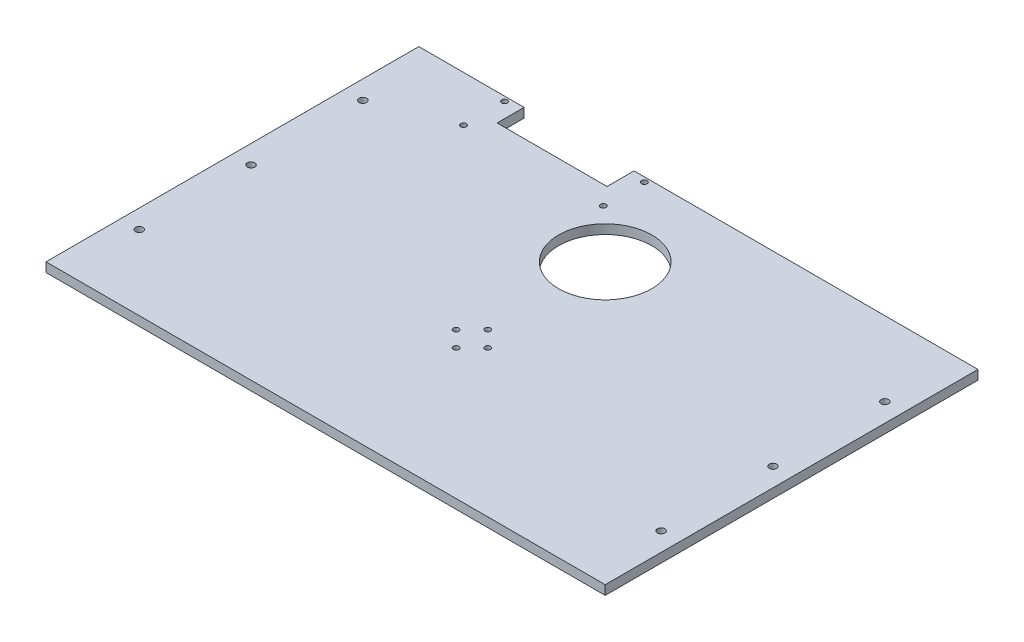
SolidWorks part; units mm, degrees
ref_plane "前视基准面" through (0, 0, 0) normal (0, 0, 1) x (1, 0, 0)
ref_plane "上视基准面" through (0, 0, 0) normal (0, 1, 0) x (1, 0, 0)
ref_plane "右视基准面" through (0, 0, 0) normal (1, 0, 0) x (0, 0, -1)
sketch "Sketch1" plane through (0, 0, 0) normal (0, 1, 0) x (1, 0, 0)
  line L1 (-150, 100) -> (150, 100)
  line L2 (-150, 100) -> (-150, -100)
  line L3 (-150, -100) -> (150, -100)
  line L4 (150, 100) -> (150, -100)
  line L5 (-150, 100) -> (150, -100) construction
  line L6 (-150, -100) -> (150, 100) construction
  point P0 (0, 0)
  dimension "D1" = 200
  dimension "D2" = 300
extrude "Boss-Extrude1" add sketch "Sketch1" along normal blind 5
sketch "Sketch2" plane through (0, 5, 0) normal (0, 1, 0) x (1, 0, 0)
  line L0 (-140, 100) -> (-140, -100) construction
  line L1 (150, 100) -> (-150, 100) construction
  line L2 (-150, -100) -> (150, -100) construction
  line L3 (-150, -90) -> (150, -90) construction
  line L4 (-150, 100) -> (-150, -100) construction
  line L5 (150, -100) -> (150, 100) construction
  line L6 (0, 0) -> (0, 100) construction
  line L7 (0, 0) -> (150, 0) construction
  line L8 (140, 100) -> (140, -100) construction
  circle A0 centre (-140, 0) radius 2
  circle A1 centre (-140, 60) radius 2
  circle A5 centre (-140, -60) radius 2
  circle A7 centre (140, -60) radius 2
  circle A8 centre (140, 60) radius 2
  circle A9 centre (140, 0) radius 2
  circle A13 centre (0, 50) radius 25
  dimension "D3" = 4
  dimension "D4" = 4
  dimension "D5" = 50
  dimension "D8" = 60
  dimension "D1" = 10
  dimension "D2" = 10
extrude "Cut-Extrude2" cut sketch "Sketch2" against normal through all
sketch "Sketch4" plane through (0, 5, 0) normal (0, 1, 0) x (1, 0, 0)
  line L0 (150, 100) -> (-150, 100) construction
  line L1 (-26.5, 97.5) -> (-101.5, 97.5) construction
  line L2 (-26.5, 97.5) -> (-26.5, 75.5) construction
  line L3 (-26.5, 75.5) -> (-101.5, 75.5) construction
  line L4 (-101.5, 97.5) -> (-101.5, 75.5) construction
  line L5 (-26.5, 97.5) -> (-101.5, 75.5) construction
  line L6 (-26.5, 75.5) -> (-101.5, 97.5) construction
  line L7 (-150, 100) -> (-150, -100) construction
  circle A0 centre (-101.5, 97.5) radius 1.5
  circle A1 centre (-26.5, 97.5) radius 1.5
  circle A2 centre (-26.5, 75.5) radius 1.5
  circle A3 centre (-101.5, 75.5) radius 1.5
  point P0 (-64, 86.5)
  dimension "D3" = 3
  dimension "D1" = 75
  dimension "D2" = 22
  dimension "D4" = 2.5
  dimension "D5" = 48.5
extrude "Cut-Extrude3" cut sketch "Sketch4" against normal through all
sketch "Sketch6" plane through (0, 0, 0) normal (0, -1, 0) x (1, 0, 0)
  line L0 (150, -100) -> (-150, -100) construction
  line L1 (-93.5, -100) -> (-34.5, -100)
  line L2 (-93.5, -100) -> (-93.5, -85.5)
  line L3 (-93.5, -85.5) -> (-34.5, -85.5)
  line L4 (-34.5, -100) -> (-34.5, -85.5)
  circle A0 centre (-101.5, -75.5) radius 1.5 construction
  circle A1 centre (-26.5, -75.5) radius 1.5 construction
  dimension "D1" = 8
  dimension "D2" = 8
  dimension "D3" = 10
extrude "Cut-Extrude4" cut sketch "Sketch6" against normal blind 5
sketch "Sketch7" plane through (0, 5, 0) normal (0, 1, 0) x (1, 0, 0)
  line L0 (0, 0) -> (0, -21.5) construction
  line L1 (0, -30) -> (0, -13) construction
  line L2 (-150, -100) -> (150, -100) construction
  circle A0 centre (0, -13) radius 1.5
  circle A1 centre (0, -30) radius 1.5
  circle A2 centre (0, -21.5) radius 8.5 construction
  circle A3 centre (-8.5, -21.5) radius 1.5
  circle A4 centre (8.5, -21.5) radius 1.5
  point P6 (0, -21.5)
  dimension "D2" = 3
  dimension "D4" = 70
  dimension "D3" = 8.5
extrude "Cut-Extrude5" cut sketch "Sketch7" against normal through all
